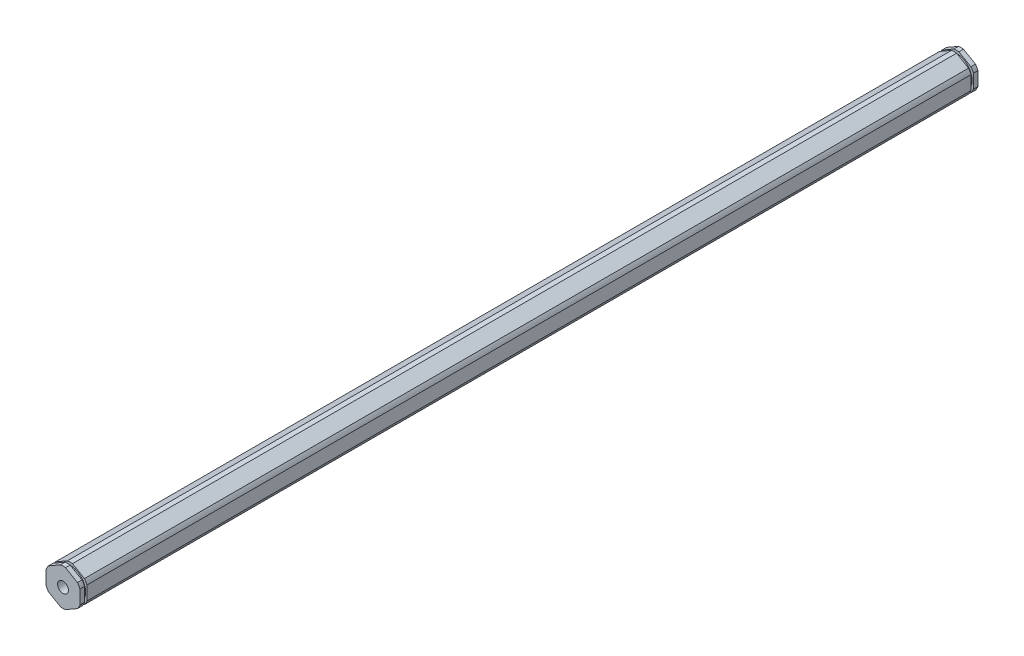
SolidWorks part; units mm, degrees
ref_plane "Front Plane" through (0, 0, 0) normal (0, 0, 1) x (1, 0, 0)
ref_plane "Top Plane" through (0, 0, 0) normal (0, 1, 0) x (1, 0, 0)
ref_plane "Right Plane" through (0, 0, 0) normal (1, 0, 0) x (0, 0, -1)
sketch "Sketch1" plane through (0, 0, 0) normal (0, 0, 1) x (1, 0, 0)
  line L1 (0, 7.3323) -> (-6.35, 3.6662)
  line L2 (-6.35, 3.6662) -> (-6.35, -3.6662)
  line L3 (-6.35, -3.6662) -> (0, -7.3323)
  line L4 (0, -7.3323) -> (6.35, -3.6662)
  line L5 (6.35, -3.6662) -> (6.35, 3.6662)
  line L6 (6.35, 3.6662) -> (0, 7.3323)
  circle A0 centre (0, 0) radius 6.35 construction
  circle A1 centre (0, 0) radius 6.858
  dimension "D1" = 12.7
  dimension "D2" = 13.716
extrude "Boss-Extrude1" add sketch "Sketch1" along normal mid plane 335.534 contours L5 A1 L6 L1 L2 L3 L4 region at (0, 0, 0)
hole_wizard "#10-32 Tapped Hole1" positions "3DSketch1" profile "Sketch2" tap size "#10-32" standard "ANSI Inch"
sketch3d "3DSketch1"
  line L0 (0, 0, 167.767) -> (0, 0, -167.767) construction
  line L1 (0, 0, 167.767) -> (0, 0, -167.767) construction
  point P0 (0, 0, 167.767)
  point P4 (0, 0, -167.767)
sketch "Sketch2" plane through (0, 0, 167.767) normal (1, 0, 0) x (0, -1, 0)
  line L0 (0, 0) -> (0, 17.5608)
  line L1 (0, 17.5608) -> (2.0193, 16.3474)
  line L2 (2.0193, 16.3474) -> (2.0193, 0)
  line L5 (2.0193, 0) -> (0, 0)
  line L10 (0, 17.5608) -> (-2.0193, 16.3474) construction
  line L11 (0, -6.35) -> (0, 107.95) construction
  dimension "Tap Drill Dia." = 4.0386
  dimension "Tap Drill Depth" = 16.3474
  dimension "Drill Angle" = 118
cosmetic thread "Hole Thread1" parameters "D1"=13.97, "D2"=4.826
cosmetic thread "Hole Thread2" parameters "D1"=13.97, "D2"=4.826
sketch "Sketch5" plane through (0, 0, 0) normal (1, 0, 0) x (0, 0, -1)
  line L0 (167.767, 6.858) -> (-167.767, 6.858) construction
  line L1 (-166.0525, 6.858) -> (-165.1635, 6.858)
  line L2 (-166.0525, 6.858) -> (-166.0525, 5.8547)
  line L3 (-166.0525, 5.8547) -> (-165.1635, 5.8547)
  line L4 (-165.1635, 6.858) -> (-165.1635, 5.8547)
  line L5 (-165.0472, 0) -> (-158.8423, 0) construction
  dimension "D1" = 5.8547
  dimension "D2" = 0.889
  dimension "D3" = 1.7145
revolve "Cut-Revolve1" cut sketch "Sketch5" angle 360 about L5
mirror "Mirror1" about plane through (0, 0, 0) normal (0, 0, 1) of "Cut-Revolve1"
